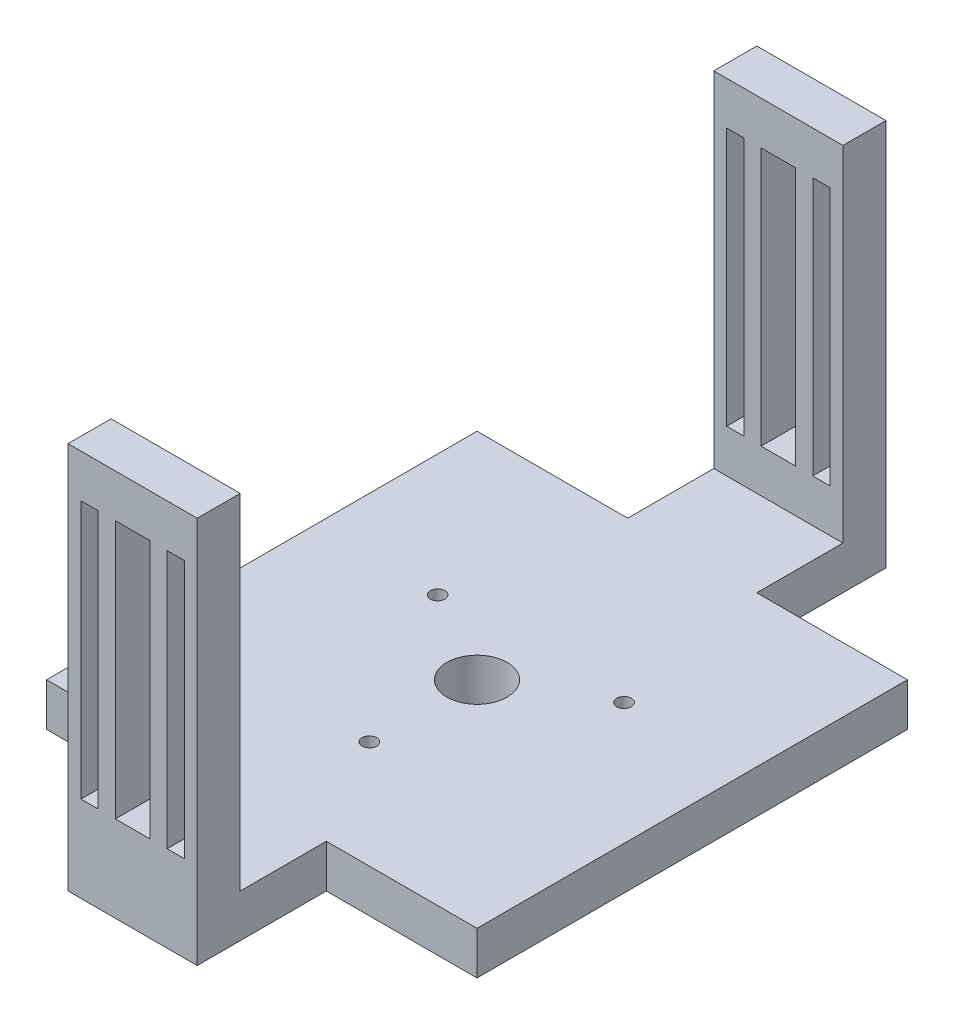
SolidWorks part; units mm, degrees
ref_plane "Plano frontal" through (0, 0, 0) normal (0, 0, 1) x (1, 0, 0)
ref_plane "Plano superior" through (0, 0, 0) normal (0, 1, 0) x (1, 0, 0)
ref_plane "Plano direito" through (0, 0, 0) normal (1, 0, 0) x (0, 0, -1)
sketch "Esboço1" plane through (0, 0, 0) normal (0, 0, 1) x (1, 0, 0)
  line L17 (-15, -40) -> (15, -40)
  line L18 (-15, -40) -> (-15, 40)
  line L19 (-15, 40) -> (15, 40)
  line L20 (15, -40) -> (15, 40)
  line L21 (-4, -30) -> (4, -30)
  line L22 (-4, -30) -> (-4, 30)
  line L23 (-4, 30) -> (4, 30)
  line L24 (4, -30) -> (4, 30)
  line L25 (-4, -30) -> (4, 30) construction
  line L26 (-4, 30) -> (4, -30) construction
  line L27 (-15, -40) -> (15, -40)
  line L28 (-15, -40) -> (-15, -50)
  line L29 (-15, -50) -> (15, -50)
  line L30 (15, -40) -> (15, -50)
  line L32 (-50, -40) -> (50, -40)
  line L33 (-50, -40) -> (-50, -50)
  line L34 (-50, -50) -> (50, -50)
  line L35 (50, -40) -> (50, -50)
  line L39 (-8, 30) -> (-12, 30)
  line L40 (-8, 30) -> (-8, -30)
  line L41 (-8, -30) -> (-12, -30)
  line L42 (-12, 30) -> (-12, -30)
  line L43 (8, 30) -> (12, 30)
  line L44 (8, 30) -> (8, -30)
  line L45 (8, -30) -> (12, -30)
  line L46 (12, 30) -> (12, -30)
  point P0 (0, 0)
extrude "Ressalto-extrusão1" add sketch "Esboço1" along normal blind 10 contours L17 L20 L19 L18 L24 L21 L22 L23 region at (-14.1456, 0, 0)
extrude "Ressalto-extrusão3" add sketch "Esboço1<4>" along normal blind 80 contours L30 L17 L28 L29 region at (0, -45, 0)
sketch "Esboço1<4>" plane through (0, 0, 0) normal (0, 0, 1) x (1, 0, 0) same geometry as "Esboço1"
ref_plane "Plano1" through (0, 0, 80) normal (0, 0, 1) x (1, 0, 0)
extrude "Ressalto-extrusão5" add sketch "Esboço1<6>" against normal blind 50 from surface contours L33 L34 L28 L32 | L35 L32 L30 L34 region at (-32.5, -45, 0) region at (32.5, -45, 0) starting at plane "Plano1"
sketch "Esboço1<6>" plane through (0, 0, 0) normal (0, 0, 1) x (1, 0, 0) same geometry as "Esboço1"
mirror "Espelhar2" about plane through (0, 0, 80) normal (0, 0, 1) of "Ressalto-extrusão5", "Ressalto-extrusão3", "Ressalto-extrusão1"
sketch "Esboço3" plane through (0, -40, 0) normal (0, 1, 0) x (1, 0, 0)
  circle A0 centre (0, -80) radius 7
  circle A1 centre (0, -105) radius 3.3
  circle A2 centre (-21.6506, -67.5) radius 3.3
  circle A3 centre (21.6506, -67.5) radius 3.3
  point P11 (0, -80)
  dimension "D1" = 3
extrude "Corte-extrusão1" cut sketch "Esboço3" against normal blind 10 contours A0
sketch "Esboço7" plane through (0, -50, 0) normal (0, -1, 0) x (-1, 0, 0)
  circle A0 centre (0, -105) radius 3.3
  circle A1 centre (-21.6506, -67.5) radius 3.3
  circle A2 centre (21.6506, -67.5) radius 3.3
hole_wizard "Rebaixo para parafuso Allen sextavado de M34" positions "Esboço10" profile "Esboço11" counterbore size "M3" standard "ISO" end condition up to next
sketch "Esboço10" plane through (0, -50, 0) normal (0, -1, 0) x (-1, 0, 0)
  point P0 (-21.6506, -67.5)
  point P3 (21.6506, -67.5)
  point P6 (0, -105)
sketch "Esboço11" plane through (21.6506, -50, 67.5) normal (1, 0, 0) x (0, 0, -1)
  line L0 (0, 0) -> (0, 10)
  line L1 (0, 10) -> (1.7, 10)
  line L3 (1.7, 10) -> (1.7, 3.4)
  line L4 (3.25, 3.4) -> (1.7, 3.4)
  line L5 (3.25, 3.4) -> (3.25, 0.025)
  line L6 (3.25, 0.025) -> (3.275, 0)
  line L7 (3.275, 0) -> (0, 0)
  line L8 (-3.25, 0.025) -> (-3.275, 0) construction
  line L11 (0, -6.35) -> (0, 107.95) construction
  dimension "Thru Hole Dia." = 3.4
  dimension "Thru Hole Depth" = 10
  dimension "C'Bore Dia." = 6.5
  dimension "C'Bore Depth" = 3.4
  dimension "Near C'Sink Dia." = 6.55
  dimension "Near C'Sink Angle" = 90
